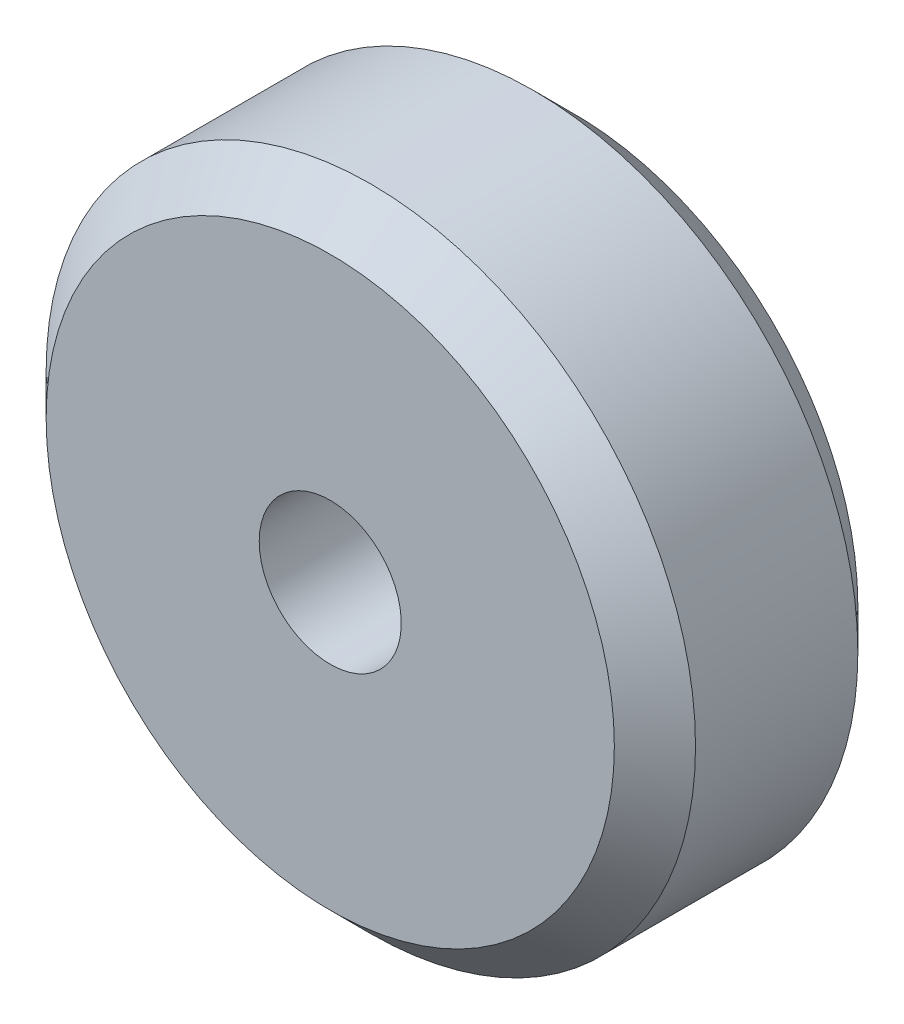
SolidWorks part; units mm, degrees
ref_plane "Appui latéral" through (0, 0, 0) normal (0, 0, 1) x (1, 0, 0)
ref_plane "Dessus" through (0, 0, 0) normal (0, 1, 0) x (1, 0, 0)
ref_plane "Droite" through (0, 0, 0) normal (1, 0, 0) x (0, 0, -1)
ref_axis "Axe1" through (0, 0, -50) along (0, 0, 1)
sketch "Esquisse1" plane through (0, 0, 0) normal (0, 0, 1) x (1, 0, 0)
  circle A0 centre (0, 0) radius 3.5
  circle A1 centre (0, 0) radius 3.5 construction
  circle A2 centre (0, 0) radius 16
  dimension "D1" = 32
extrude "Base-Extrusion" add sketch "Esquisse1" along normal up to surface (12 mm away)
chamfer "Chanfrein1" distance 2 angle 45 2 edges at (-16, 0, 12) (16, 0, 0)
